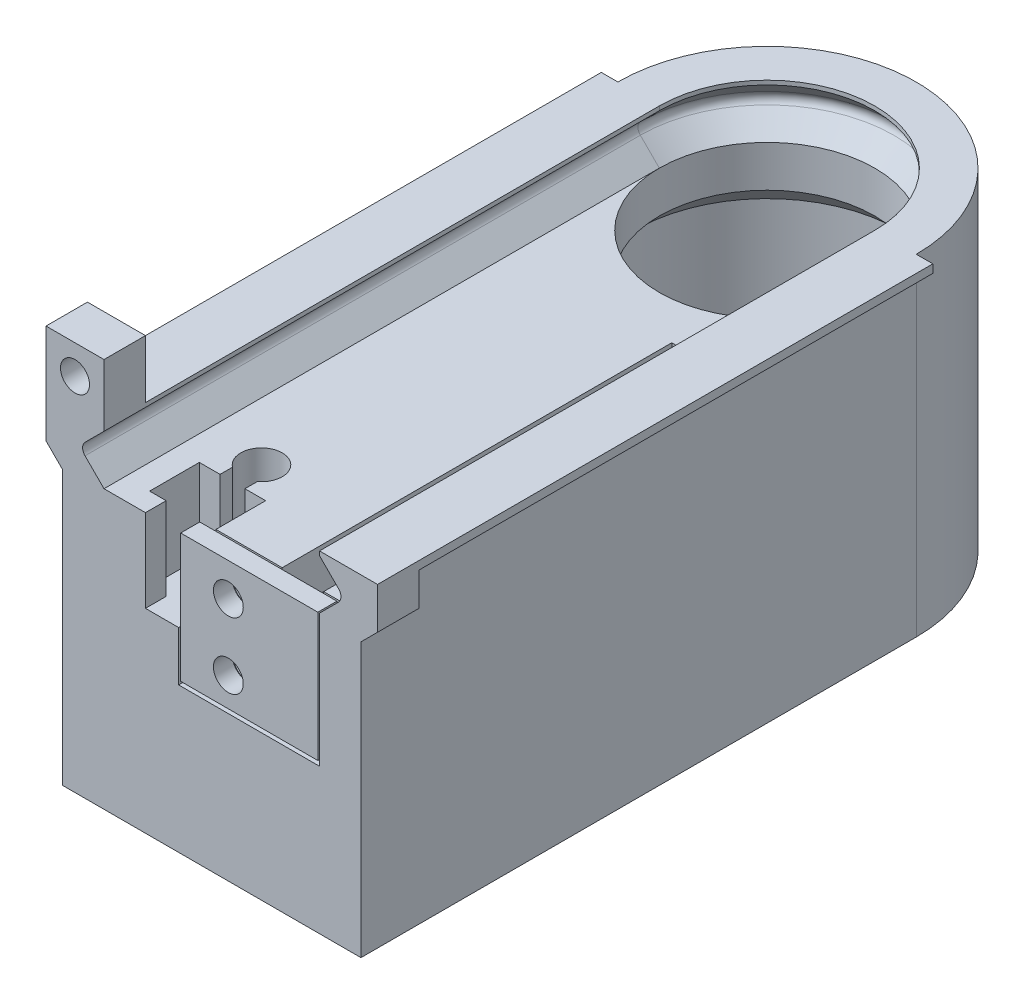
SolidWorks part; units mm, degrees
ref_plane "Płaszczyzna przednia" through (0, 0, 0) normal (0, 0, 1) x (1, 0, 0)
ref_plane "Płaszczyzna górna" through (0, 0, 0) normal (0, 1, 0) x (1, 0, 0)
ref_plane "Płaszczyzna prawa" through (0, 0, 0) normal (1, 0, 0) x (0, 0, -1)
sketch "Szkic1" plane through (0, 0, 0) normal (0, 1, 0) x (1, 0, 0)
  line L0 (0, -33.5) -> (0, 51.5) construction
  line L1 (-18, 33.5) -> (18, 33.5)
  line L2 (-18, 33.5) -> (-18, -33.5)
  line L3 (-18, -33.5) -> (18, -33.5)
  line L4 (18, 33.5) -> (18, -33.5)
  line L5 (-18, 33.5) -> (18, -33.5) construction
  line L6 (-18, -33.5) -> (18, 33.5) construction
  circle A0 centre (0, 33.5) radius 18
  point P0 (0, 0)
  dimension "D1" = 36
  dimension "D2" = 85
extrude "Dodanie-wyciągnięcie1" add sketch "Szkic1" along normal blind 40 contours A0 L2 L3 L4 | L1 A0 | A0 region at (0, 0, -41.1394) region at (0, 0, 6.9159)
sketch "Szkic2" plane through (0, 40, 0) normal (0, 1, 0) x (1, 0, 0)
  line L3 (-13, -33.5) -> (13, -33.5)
  line L5 (13, -33.5) -> (13, 33.5)
  line L6 (-13, 33.5) -> (-13, -33.5)
  line L7 (13, -33.5) -> (13, 33.5)
  line L8 (-13, 33.5) -> (-13, -33.5)
  arc A5 (13, 33.5) -> (-13, 33.5) centre (0, 33.5) ccw
  arc A6 (13, 33.5) -> (-13, 33.5) centre (0, 33.5) ccw
  dimension "D1" = 5
extrude "Wytnij-wyciągnięcie1" cut sketch "Szkic2" against normal blind 6.5
sketch "Szkic4" plane through (0, 0, 33.5) normal (0, 0, 1) x (1, 0, 0)
  line L0 (13, 33.5) -> (16, 36.5)
  line L1 (16, 36.5) -> (13, 39.5)
  line L2 (13, 33.5) -> (13, 40) construction
  line L3 (13, 39.5) -> (13, 33.5)
  dimension "D1" = 6
  dimension "D2" = 45
sketch "Szkic5" plane through (0, 40, 0) normal (0, 1, 0) x (1, 0, 0)
  line L0 (13, -33.5) -> (13, 33.5) construction
  line L1 (-13, 33.5) -> (-13, -33.5) construction
  line L2 (13, -33.5) -> (13, 33.5)
  line L3 (-13, 33.5) -> (-13, -33.5)
  arc A0 (13, 33.5) -> (-13, 33.5) centre (0, 33.5) ccw construction
  arc A1 (13, 33.5) -> (-13, 33.5) centre (0, 33.5) ccw
sweep "Wycięcie-wyciągnięcie po ścieżce1" cut profiles "Szkic4" path "Szkic5"
sketch "Szkic6" plane through (0, 33.5, 0) normal (0, 1, 0) x (1, 0, 0)
  circle A0 centre (0, 33.5) radius 13
extrude "Wytnij-wyciągnięcie2" cut sketch "Szkic6" against normal blind 30
sketch "Szkic7" plane through (0, 3.5, 0) normal (0, 1, 0) x (1, 0, 0)
  circle A0 centre (0, 33.5) radius 16
  arc A5 (18, 33.5) -> (-18, 33.5) centre (0, 33.5) ccw construction
  dimension "D1" = 2
extrude "Wytnij-wyciągnięcie4" cut sketch "Szkic7" along normal blind 20
chamfer "Sfazowanie1" distance 5 angle 45 1 edges at (0, 23.5, -20.5)
sketch "Szkic8" plane through (0, 33.5, 0) normal (0, 1, 0) x (1, 0, 0)
  line L0 (-13, -33.5) -> (13, -33.5) construction
  line L1 (11, 16) -> (6, 16)
  line L2 (11, 16) -> (11, -31)
  line L3 (11, -31) -> (6, -31)
  line L4 (6, 16) -> (6, -31)
  line L5 (11, 16) -> (6, -31) construction
  line L6 (11, -31) -> (6, 16) construction
  line L7 (13, -33.5) -> (13, 33.5) construction
  point P0 (8.5, -7.5)
  dimension "D1" = 5
  dimension "D2" = 2.5
  dimension "D3" = 47
  dimension "D4" = 2
extrude "Wytnij-wyciągnięcie5" cut sketch "Szkic8" against normal blind 5
fillet "Zaokrąglenie2" radius 1 3 edges at (-16, 36.5, 0) (0, 36.5, -49.5) (16, 36.5, 0)
ref_plane "Płaszczyzna1" through (13, 40, 33.5) normal (0, 0, -1) x (-1, 0, 0)
sketch "Szkic10" plane through (0, 33.5, 0) normal (0, 1, 0) x (1, 0, 0)
  line L0 (-6, -28) -> (-13.5, -28) construction
  line L1 (-2, -31) -> (-10, -31)
  line L2 (-2, -31) -> (-2, -25)
  line L3 (-2, -25) -> (-10, -25)
  line L4 (-10, -31) -> (-10, -25)
  line L5 (-2, -31) -> (-10, -25) construction
  line L6 (-2, -25) -> (-10, -31) construction
  line L7 (6, -31) -> (11, -31) construction
  line L14 (0, 0) -> (0, -47.4858) construction
  line L16 (-6, -28) -> (-6, -21.5) construction
  line L18 (-4.5, -25) -> (-7.5, -25)
  line L19 (-4.5, -25) -> (-4.5, -23.5)
  line L20 (-4.5, -23.5) -> (-7.5, -23.5)
  line L21 (-7.5, -25) -> (-7.5, -23.5)
  line L22 (-4.5, -25) -> (-7.5, -23.5) construction
  line L23 (-4.5, -23.5) -> (-7.5, -25) construction
  circle A1 centre (-6, -21.5) radius 2.5
  point P0 (-6, -28)
  point P21 (-6, -24.25)
  dimension "D7" = 5
  dimension "D1" = 8
  dimension "D2" = 6
  dimension "D6" = 2
  dimension "D8" = 3
  dimension "D9" = 1.5
extrude "Wytnij-wyciągnięcie6" cut sketch "Szkic10" against normal blind 10 contours L4 L1 L2 L3 | L20 A1 | A1 L21 L3 L19 | L20 A1 region at (-6, 33.5, 28) region at (-6, 33.5, 24.4111) region at (-6, 33.5, 23.7018) region at (-6, 33.5, 21.3791)
sketch "Szkic26" plane through (0, 23.5, 0) normal (0, 1, 0) x (1, 0, 0)
  circle A0 centre (-6, -21.5) radius 2.5
extrude "Wytnij-wyciągnięcie10" cut sketch "Szkic26" against normal blind 21
sketch "Szkic12" plane through (0, 33.5, 0) normal (0, 1, 0) x (1, 0, 0)
  line L0 (-6, -24) -> (-6, -37.0219) construction
  line L11 (-2, -31) -> (-10, -31) construction
  line L12 (-4, -33.5) -> (-8, -33.5)
  line L13 (-4, -33.5) -> (-4, -31)
  line L14 (-4, -31) -> (-8, -31)
  line L15 (-8, -33.5) -> (-8, -31)
  line L16 (-4, -33.5) -> (-8, -31) construction
  line L17 (-4, -31) -> (-8, -33.5) construction
  line L18 (-13, -33.5) -> (13, -33.5) construction
  arc A0 (-7.5, -23.5) -> (-4.5, -23.5) centre (-6, -21.5) ccw construction
  point P2 (-6, -32.25)
  line M10 (-2, -31) -> (-10, -31)
  line M19 (-13, -33.5) -> (13, -33.5)
  dimension "D1" = 4
extrude "Wytnij-wyciągnięcie8" cut sketch "Szkic12" against normal up to surface (10 mm away) contours L15 L13 M19 M10 region at (-6, 33.5, 32.25) up to face at (-6, 23.5, 26.1875)
sketch "Szkic13" plane through (0, 0, 33.5) normal (0, 0, 1) x (1, 0, 0)
  line L0 (-18, 40) -> (-20, 40)
  line L1 (-18, 40) -> (-18, 0) construction
  line L2 (-20, 40) -> (-20, 39)
  line L3 (-20, 39) -> (-18, 37)
  line L4 (-18, 37) -> (-18, 40)
  line L5 (0, 0) -> (0, 45.7075) construction
  line L6 (-18, 0) -> (18, 0) construction
  line L7 (18, 37) -> (18, 40)
  line L8 (20, 39) -> (18, 37)
  line L9 (20, 40) -> (20, 39)
  line L10 (18, 40) -> (20, 40)
  dimension "D1" = 2
  dimension "D2" = 1
  dimension "D3" = 45
extrude "Dodanie-wyciągnięcie2" add sketch "Szkic13" against normal up to vertex (67 mm away) up to point (-18, 40, -33.5)
sketch "Szkic17" plane through (0, 33.5, 0) normal (0, 1, 0) x (1, 0, 0)
  line L0 (13, -33.5) -> (13, 33.5) construction
  line L1 (-4, -33.5) -> (13, -33.5)
  line L2 (-4, -33.5) -> (-4, -31)
  line L3 (-4, -31) -> (13, -31)
  line L4 (13, -33.5) -> (13, -31)
  line L5 (6, -31) -> (11, -31) construction
  line L6 (-2, -31) -> (-4, -31) construction
  line L7 (-4, -33.5) -> (-4, -31) construction
extrude "Wytnij-wyciągnięcie9" cut sketch "Szkic17" against normal blind 16
sketch "Szkic18" plane through (0, 0, 31) normal (0, 0, 1) x (1, 0, 0)
  line L3 (6, 33.5) -> (-2, 33.5) construction
  line L4 (13, 17.5) -> (-4, 17.5) construction
  line L6 (2, 29.5) -> (2, 33.5) construction
  line L7 (2, 29.5) -> (2, 21.5) construction
  line L8 (2, 21.5) -> (2, 17.5) construction
  circle A0 centre (2, 29.5) radius 2
  circle A1 centre (2, 21.5) radius 2
  point P6 (2, 29.5)
  point P8 (2, 21.5)
  dimension "D1" = 4
  dimension "D2" = 8
sketch "Szkic22" plane through (0, 0, 31) normal (0, 0, 1) x (1, 0, 0)
  point P0 (2, 29.5)
  point P3 (2, 21.5)
hole_wizard "Otwory ustalające Ø4.0mm5" positions "Szkic22" profile "Szkic21" hole size "Ø4.0" standard "DIN"
sketch "Szkic21" plane through (2, 29.5, 31) normal (1, 0, 0) x (0, -1, 0)
  line L0 (0, 0) -> (0, 16.2017)
  line L1 (0, 16.2017) -> (2, 15)
  line L2 (2, 15) -> (2, 0)
  line L5 (2, 0) -> (0, 0)
  line L10 (0, 16.2017) -> (-2, 15) construction
  line L11 (0, -6.35) -> (0, 107.95) construction
  dimension "Średnica otworu" = 4
  dimension "Głębokość otworu" = 15
  dimension "Kąt wiertła" = 118
sketch "Szkic23" plane through (0, 33.5, 0) normal (0, 1, 0) x (1, 0, 0)
  line L1 (-3.75, -31.2) -> (12.8, -31.2)
  line L2 (-3.75, -31.2) -> (-3.75, -33.5)
  line L3 (-3.75, -33.5) -> (12.8, -33.5)
  line L4 (-4, -31) -> (-4, -33.5)
  line L5 (-4, -33.5) -> (13, -33.5)
  line L6 (13, -33.5) -> (13, -31)
  line L7 (13, -31) -> (-4, -31)
  line L8 (-4, -31) -> (-4, -33.5) construction
  line L9 (-4, -33.5) -> (13, -33.5) construction
  line L10 (13, -33.5) -> (13, -31) construction
  line L11 (13, -31) -> (-4, -31) construction
  line L12 (12.8, -31.2) -> (12.8, -33.5)
  dimension "D2" = 0.5
  dimension "D3" = 0.2
  dimension "D4" = 0.2
  dimension "D1" = 0
extrude "Dodanie-wyciągnięcie4" add sketch "Szkic23" against normal blind 15.5 separate body
sketch "Szkic24" plane through (0, 0, 33.5) normal (0, 0, 1) x (1, 0, 0)
  circle A0 centre (2, 21.5) radius 2 construction
  circle A1 centre (2, 29.5) radius 2 construction
  circle A2 centre (2, 21.5) radius 2
  circle A3 centre (2, 29.5) radius 2
  point P0 (2, 21.5)
  point P2 (2, 29.5)
hole_wizard "Otwory ustalające Ø4.0mm6" positions "Szkic24" profile "Szkic25" hole size "Ø4.0" standard "DIN"
sketch "Szkic25" plane through (2, 21.5, 33.5) normal (1, 0, 0) x (0, -1, 0)
  line L0 (0, 0) -> (0, 16.0815)
  line L1 (0, 16.0815) -> (1.8, 15)
  line L2 (1.8, 15) -> (1.8, 0)
  line L5 (1.8, 0) -> (0, 0)
  line L10 (0, 16.0815) -> (-1.8, 15) construction
  line L11 (0, -6.35) -> (0, 107.95) construction
  dimension "Średnica otworu" = 3.6
  dimension "Głębokość otworu" = 15
  dimension "Kąt wiertła" = 118
sketch "Szkic27" plane through (0, 0, 33.5) normal (0, 0, 1) x (1, 0, 0)
  line L0 (0, 0) -> (0, 27.1051) construction
  line L1 (-20, 39) -> (-20, 35)
  line L3 (-20, 39) -> (-18, 37) construction
  line L4 (-20, 40) -> (-20, 39) construction
  line L5 (-20, 35) -> (-18, 35)
  line L6 (-18, 37) -> (-18, 0) construction
  line L7 (-18, 35) -> (-18, 37)
  line L8 (-18, 37) -> (-20, 39)
  line L9 (18, 37) -> (20, 39)
  line L10 (18, 35) -> (18, 37)
  line L11 (20, 35) -> (18, 35)
  line L12 (20, 39) -> (20, 35)
  dimension "D1" = 4
extrude "Dodanie-wyciągnięcie5" add sketch "Szkic27" against normal blind 5
chamfer "Sfazowanie2" distance 2 angle 45 2 edges at (18, 35, 31) (-18, 35, 31)
sketch "Szkic29" plane through (0, 0, 28.5) normal (0, 0, -1) x (-1, 0, 0)
  line L0 (16.5, 40) -> (16.5, 43.5) construction
  line L1 (20, 40) -> (13, 40) construction
  line L2 (16.5, 41.75) -> (16.5, 40) construction
  line L3 (20, 40) -> (20, 35) construction
  line L4 (13, 47) -> (20, 47)
  line L5 (13, 47) -> (13, 40)
  line L6 (13, 40) -> (20, 40)
  line L7 (20, 47) -> (20, 40)
  line L8 (13, 47) -> (20, 40) construction
  line L9 (13, 40) -> (20, 47) construction
  circle A0 centre (16.5, 43.5) radius 1.75
  point P10 (19.716, 39.784)
  point P11 (20, 40)
  point P14 (20, 40)
  dimension "3,5" = 3.5
extrude "Dodanie-wyciągnięcie6" add sketch "Szkic29" against normal blind 5
